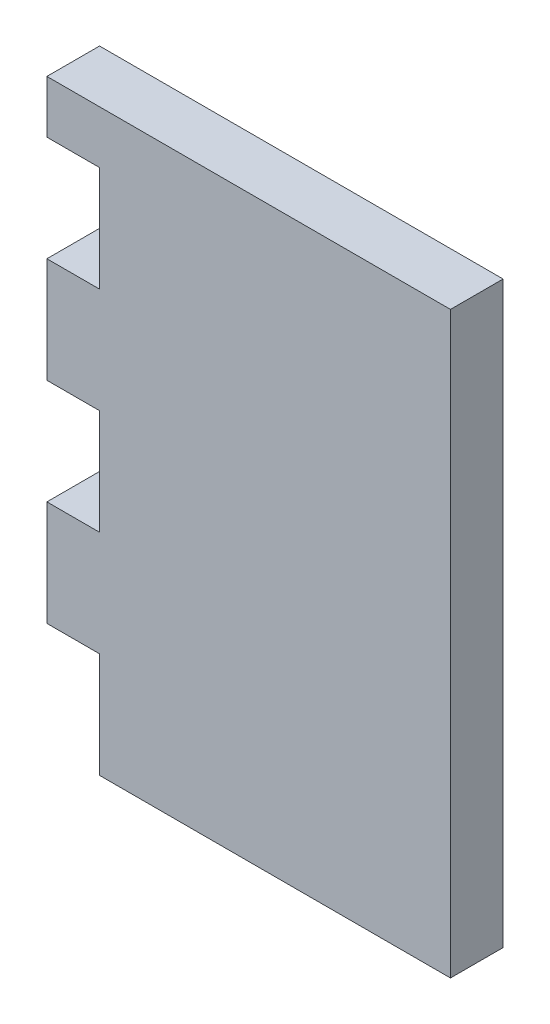
SolidWorks part; units mm, degrees
material "Pine"
ref_plane "Front Plane" through (0, 0, 0) normal (0, 0, 1) x (1, 0, 0)
ref_plane "Top Plane" through (0, 0, 0) normal (0, 1, 0) x (1, 0, 0)
ref_plane "Right Plane" through (0, 0, 0) normal (1, 0, 0) x (0, 0, -1)
sketch "Sketch1" plane through (0, 0, 0) normal (0, 0, 1) x (1, 0, 0)
  line L0 (0, -42) -> (0, -30)
  line L5 (0, 0) -> (46, 0)
  line L6 (0, 0) -> (0, -66)
  line L7 (0, -66) -> (46, -66)
  line L8 (46, 0) -> (46, -66)
  line L9 (0, -66) -> (6, -66)
  line L10 (0, -66) -> (0, -54)
  line L11 (0, -54) -> (6, -54)
  line L12 (6, -66) -> (6, -54)
  line L13 (0, -42) -> (6, -42)
  line L14 (6, -42) -> (6, -30)
  line L15 (0, -30) -> (6, -30)
  line L16 (0, -18) -> (0, -6)
  line L17 (0, -18) -> (6, -18)
  line L18 (6, -18) -> (6, -6)
  line L19 (0, -6) -> (6, -6)
  dimension "D1" = 66
  dimension "D2" = 46
  dimension "D3" = 6
  dimension "D4" = 12
  dimension "D5" = 3
extrude "Boss-Extrude1" add sketch "Sketch1" along normal blind 6 contours L6 L19 L18 L17 L15 L14 L13 L11 L12 L7 L8 L5 region at (24.5319, -32.7702, 0)
